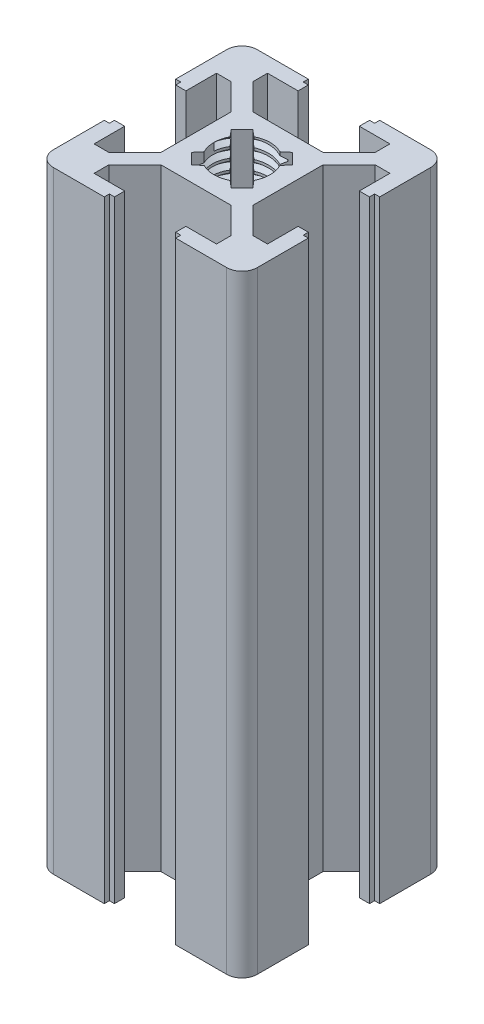
SolidWorks part; units mm, degrees
material "3.3547 (EN-AW 5083)"
ref_plane "Płaszczyzna przednia" through (0, 0, 0) normal (0, 0, 1) x (1, 0, 0)
ref_plane "Płaszczyzna górna" through (0, 0, 0) normal (0, 1, 0) x (1, 0, 0)
ref_plane "Płaszczyzna prawa" through (0, 0, 0) normal (1, 0, 0) x (0, 0, -1)
sketch "Szkic1" plane through (0, 0, 0) normal (0, 1, 0) x (1, 0, 0)
  line L0 (0, 10) -> (0, -10) construction
  line L1 (4.5, -4.5) -> (-4.5, -4.5)
  line L2 (4.5, -4.5) -> (4.5, 4.5)
  line L3 (4.5, 4.5) -> (-4.5, 4.5)
  line L4 (-4.5, -4.5) -> (-4.5, 4.5)
  line L5 (4.5, -4.5) -> (-4.5, 4.5) construction
  line L6 (4.5, 4.5) -> (-4.5, -4.5) construction
  line L7 (8.5, -10) -> (-8.5, -10)
  line L8 (10, -8.5) -> (10, 8.5)
  line L9 (8.5, 10) -> (-8.5, 10)
  line L10 (-10, -8.5) -> (-10, 8.5)
  line L11 (10, -10) -> (-10, 10) construction
  line L12 (10, 10) -> (-10, -10) construction
  line L13 (3.5, 10) -> (-3.5, 10)
  line L14 (-3.5, 10) -> (-3.5, 9.5)
  line L15 (-3.5, 9.5) -> (-3, 9.5)
  line L16 (-3, 9.5) -> (-3, 8.5)
  line L17 (-3, 8.5) -> (-6, 8.5)
  line L18 (-6, 8.5) -> (-6, 7.06)
  line L19 (-6, 7.06) -> (-3.4405, 4.5)
  line L20 (-1.9445, 3.0052) -> (-3.0052, 1.9445)
  line L21 (-1.9445, 3.0052) -> (-1.2713, 2.4385)
  line L22 (-3.0052, 1.9445) -> (-2.4385, 1.2713)
  line L23 (3.5, 10) -> (3.5, 9.5)
  line L24 (3.5, 9.5) -> (3, 9.5)
  line L25 (3, 9.5) -> (3, 8.5)
  line L26 (3, 8.5) -> (6, 8.5)
  line L27 (6, 8.5) -> (6, 7.06)
  line L28 (6, 7.06) -> (3.4405, 4.5)
  line L29 (1.9445, 3.0052) -> (3.0052, 1.9445)
  line L30 (1.9445, 3.0052) -> (1.2713, 2.4385)
  line L31 (3.0052, 1.9445) -> (2.4385, 1.2713)
  line L32 (1.9445, 3.0052) -> (1.2713, 2.4385)
  line L33 (3.0052, 1.9445) -> (1.9445, 3.0052)
  line L34 (3.0052, 1.9445) -> (2.4385, 1.2713)
  line L35 (7.06, 6) -> (4.5, 3.4405)
  line L36 (8.5, 6) -> (7.06, 6)
  line L37 (8.5, 3) -> (8.5, 6)
  line L38 (9.5, 3) -> (8.5, 3)
  line L39 (9.5, 3.5) -> (9.5, 3)
  line L40 (10, 3.5) -> (9.5, 3.5)
  line L41 (10, -3.5) -> (9.5, -3.5)
  line L42 (9.5, -3.5) -> (9.5, -3)
  line L43 (9.5, -3) -> (8.5, -3)
  line L44 (8.5, -3) -> (8.5, -6)
  line L45 (8.5, -6) -> (7.06, -6)
  line L46 (7.06, -6) -> (4.5, -3.4405)
  line L47 (3.0052, -1.9445) -> (2.4385, -1.2713)
  line L48 (3.0052, -1.9445) -> (1.9445, -3.0052)
  line L49 (1.9445, -3.0052) -> (1.2713, -2.4385)
  line L50 (3.0052, -1.9445) -> (2.4385, -1.2713)
  line L51 (1.9445, -3.0052) -> (3.0052, -1.9445)
  line L52 (1.9445, -3.0052) -> (1.2713, -2.4385)
  line L53 (6, -7.06) -> (3.4405, -4.5)
  line L54 (6, -8.5) -> (6, -7.06)
  line L55 (3, -8.5) -> (6, -8.5)
  line L56 (3, -9.5) -> (3, -8.5)
  line L57 (3.5, -9.5) -> (3, -9.5)
  line L58 (3.5, -10) -> (3.5, -9.5)
  line L59 (-3.5, -10) -> (-3.5, -9.5)
  line L60 (-3.5, -9.5) -> (-3, -9.5)
  line L61 (-3, -9.5) -> (-3, -8.5)
  line L62 (-3, -8.5) -> (-6, -8.5)
  line L63 (-6, -8.5) -> (-6, -7.06)
  line L64 (-6, -7.06) -> (-3.4405, -4.5)
  line L65 (-1.9445, -3.0052) -> (-1.2713, -2.4385)
  line L66 (-1.9445, -3.0052) -> (-3.0052, -1.9445)
  line L67 (-3.0052, -1.9445) -> (-2.4385, -1.2713)
  line L68 (-1.9445, -3.0052) -> (-1.2713, -2.4385)
  line L69 (-3.0052, -1.9445) -> (-1.9445, -3.0052)
  line L70 (-3.0052, -1.9445) -> (-2.4385, -1.2713)
  line L71 (-7.06, -6) -> (-4.5, -3.4405)
  line L72 (-8.5, -6) -> (-7.06, -6)
  line L73 (-8.5, -3) -> (-8.5, -6)
  line L74 (-9.5, -3) -> (-8.5, -3)
  line L75 (-9.5, -3.5) -> (-9.5, -3)
  line L76 (-10, -3.5) -> (-9.5, -3.5)
  line L77 (-10, 3.5) -> (-9.5, 3.5)
  line L78 (-9.5, 3.5) -> (-9.5, 3)
  line L79 (-9.5, 3) -> (-8.5, 3)
  line L80 (-8.5, 3) -> (-8.5, 6)
  line L81 (-8.5, 6) -> (-7.06, 6)
  line L82 (-7.06, 6) -> (-4.5, 3.4405)
  line L83 (-3.0052, 1.9445) -> (-2.4385, 1.2713)
  line L84 (-3.0052, 1.9445) -> (-1.9445, 3.0052)
  line L85 (-1.9445, 3.0052) -> (-1.2713, 2.4385)
  circle A0 centre (0, 0) radius 2.75
  arc A1 (10, -8.5) -> (8.5, -10) centre (8.5, -8.5) cw
  arc A2 (-10, -8.5) -> (-8.5, -10) centre (-8.5, -8.5) ccw
  arc A3 (10, 8.5) -> (8.5, 10) centre (8.5, 8.5) ccw
  arc A4 (-8.5, 10) -> (-10, 8.5) centre (-8.5, 8.5) ccw
  point P16 (0, 10)
  point P37 (-2.4749, 2.4749)
  dimension "D1" = 5.5
  dimension "D12" = 1.5
  dimension "D2" = 9
  dimension "D3" = 20
  dimension "D4" = 20
  dimension "D5" = 7
  dimension "D6" = 0.5
  dimension "D7" = 0.5
  dimension "D8" = 1
  dimension "D9" = 3
  dimension "D10" = 1.44
  dimension "D11" = 3.62
  dimension "D13" = 1.5
  dimension "D14" = 3.5
  dimension "D15" = 0.88
  dimension "D16" = 4
extrude "Dodanie-wyciągnięcie1" add sketch "Szkic1" along normal blind 60 contours L9 A4 L10 L77 L78 L79 L80 L81 L82 L4 L3 L19 L18 L17 L16 L15 L14 | L8 A3 L9 L23 L24 L25 L26 L27 L28 L3 L2 L35 L36 L37 L38 L39 L40 | L4 L1 L2 L3 A0 L47 L48 L49 L65 L66 L67 L22 L20 L21 L30 L29 L31 | L10 A2 L7 L59 L60 L61 L62 L63 L64 L1 L4 L71 L72 L73 L74 L75 L76 | A1 L8 L41 L42 L43 L44 L45 L46 L2 L1 L53 L54 L55 L56 L57 L58 L7 region at (7.2228, 0, 7.2228) region at (3.9703, 0, 4.3727) region at (-7.2228, 0, 7.2228) region at (7.2228, 0, -7.2228) region at (-7.2228, 0, -7.2228)
thread "Thread1" pitch 1 method cut profile "Thread Profile1" start angle 0, offset 0, length 20, pitch 1, diameter 5.5
ref_plane "Plane1" through (-2.75, 60, 0) normal (0, 0, 1) x (-1, 0, 0)
sketch "Thread Profile1" plane through (-2.75, 60, 0) normal (0, 0, 1) x (-1, 0, 0)
  line L0 (0, 0) -> (0, 1) construction
  line L1 (0, 0) -> (0.5413, 0.3125)
  line L2 (0.5413, 0.3125) -> (0.5413, 0.4375)
  line L3 (0.5413, 0.4375) -> (0, 0.75)
  line L4 (0.5413, 0.375) -> (0, 0.375) construction
  line L11 (0, 0) -> (0, 0.75)
  point P2 (0, 0)
  dimension "Pitch" = 1
  dimension "Profile_Angle" = 60
  dimension "Profile_Land" = 0.125
  dimension "Profile_Height" = 0.5413
thread "Thread2" pitch 1 method cut profile "Thread Profile2" start angle 0, offset 0, length 20, pitch 1, diameter 5.5
ref_plane "Plane2" through (2.75, 0, 0) normal (0, 0, 1) x (1, 0, 0)
sketch "Thread Profile2" plane through (2.75, 0, 0) normal (0, 0, 1) x (1, 0, 0)
  line L0 (0, 0) -> (0, 1) construction
  line L1 (0, 0) -> (0.5413, 0.3125)
  line L2 (0.5413, 0.3125) -> (0.5413, 0.4375)
  line L3 (0.5413, 0.4375) -> (0, 0.75)
  line L4 (0.5413, 0.375) -> (0, 0.375) construction
  line L11 (0, 0) -> (0, 0.75)
  point P2 (0, 0)
  dimension "Pitch" = 1
  dimension "Profile_Angle" = 60
  dimension "Profile_Land" = 0.125
  dimension "Profile_Height" = 0.5413
